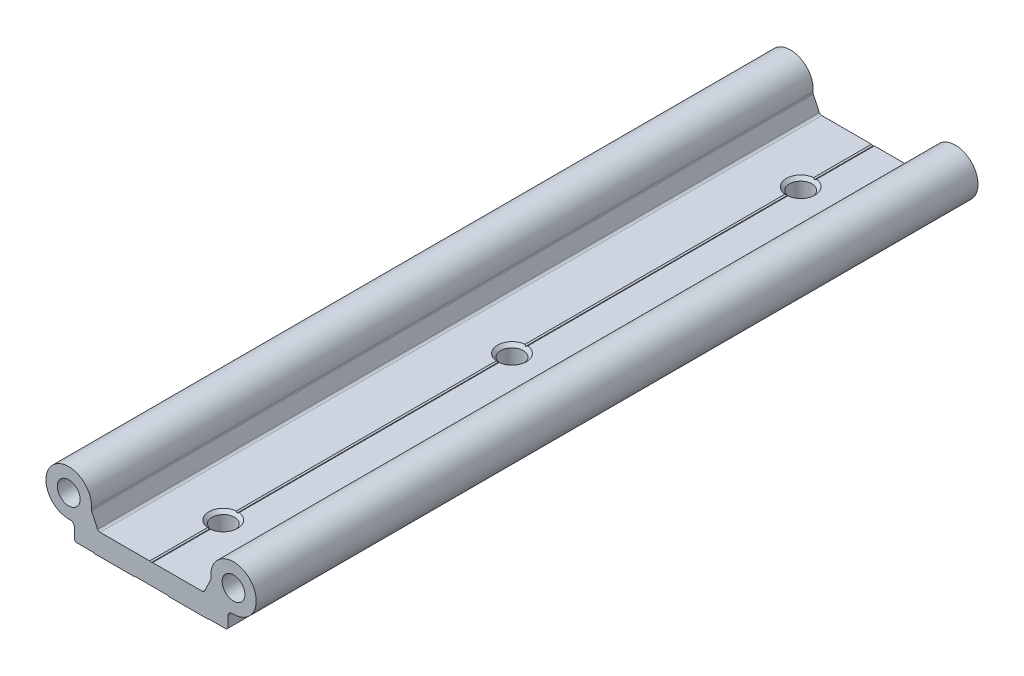
SolidWorks part; units mm, degrees
ref_plane "Front Plane" through (0, 0, 0) normal (0, 0, 1) x (1, 0, 0)
ref_plane "Top Plane" through (0, 0, 0) normal (0, 1, 0) x (1, 0, 0)
ref_plane "Right Plane" through (0, 0, 0) normal (1, 0, 0) x (0, 0, -1)
sketch "Model" plane through (0, 0, 0) normal (0, 0, 1) x (1, 0, 0)
  line L0 (0, 0.2) -> (0, 7.5) construction
  line L1 (0, 0.2) -> (0, 7.5) construction
  line L2 (0, 0.2) -> (0, 7.5) construction
  line L3 (0, 0.2) -> (0, 7.5) construction
  line L4 (-33, 14) -> (-25, 14) construction
  line L5 (25, 14) -> (33, 14) construction
  line L6 (-29, 22) -> (-29, 6) construction
  line L7 (-37, 14) -> (-21, 14) construction
  line L8 (29, 22) -> (29, 6) construction
  line L9 (21, 14) -> (37, 14) construction
  line L10 (-18.8438, 7.9819) -> (-20.9669, 12.5349)
  line L11 (6, 0) -> (5.8, 0.2)
  line L12 (-26.5, 0.2) -> (-27, 0.7)
  line L13 (-20, 0) -> (-20.2, 0.2)
  line L14 (0, 7.2113) -> (-0.5, 7.5)
  line L15 (6, 0) -> (20, 0)
  line L16 (-20, 0) -> (-6, 0)
  line L17 (-5.8, 0.2) -> (5.8, 0.2)
  line L18 (20.2, 0.2) -> (26.5, 0.2)
  line L19 (-26.5, 0.2) -> (-20.2, 0.2)
  line L20 (0.5, 7.5) -> (17.9885, 7.5)
  line L21 (-17.9885, 7.5) -> (-0.5, 7.5)
  line L22 (0, 7.2113) -> (0.5, 7.5)
  line L23 (20, 0) -> (20.2, 0.2)
  line L24 (-6, 0) -> (-5.8, 0.2)
  line L25 (26.5, 0.2) -> (27, 0.7)
  line L26 (18.8438, 7.9819) -> (20.9669, 12.5349)
  line L27 (-27, 0.7) -> (-27, 4.5132)
  line L28 (27, 0.7) -> (27, 4.5132)
  circle A0 centre (-29, 14) radius 4
  arc A1 (-21.0538, 13.0733) -> (-28.5789, 6.0111) centre (-29, 14) ccw
  arc A2 (-27, 4.5132) -> (-28.5789, 6.0111) centre (-28.5, 4.5132) ccw
  arc A3 (-21.0538, 13.0733) -> (-20.9669, 12.5349) centre (-20.0606, 12.9575) ccw
  arc A4 (-18.8438, 7.9819) -> (-17.9885, 7.5) centre (-17.9885, 8.5) ccw
  arc A5 (17.9885, 7.5) -> (18.8438, 7.9819) centre (17.9885, 8.5) ccw
  arc A6 (20.9669, 12.5349) -> (21.0538, 13.0733) centre (20.0606, 12.9575) ccw
  arc A7 (28.5789, 6.0111) -> (27, 4.5132) centre (28.5, 4.5132) ccw
  circle A8 centre (29, 14) radius 4
  arc A9 (28.5789, 6.0111) -> (21.0538, 13.0733) centre (29, 14) ccw
  dimension "D1" = 8
  dimension "D2" = 8
  dimension "D3" = 1.5
  dimension "D4" = 1
  dimension "D5" = 0.5
  dimension "D6" = 5.8
  dimension "D7" = 6
  dimension "D8" = 17.9885
  dimension "D9" = 18.8438
  dimension "D10" = 20
  dimension "D11" = 20.0606
  dimension "D12" = 20.9669
  dimension "D13" = 21.0538
  dimension "D14" = 26.5
  dimension "D15" = 27
  dimension "D16" = 4.5132
  dimension "D17" = 7.2113
extrude "Boss-Extrude1" add sketch "Model" along normal blind 254
hole_wizard "3/8-16 Tapped Hole1" positions "Sketch1" profile "Sketch2" tap size "3/8-16" standard "ANSI Inch" end condition through all
sketch "Sketch1" plane through (0, 7.5, 0) normal (0, 1, 0) x (1, 0, 0)
  line L0 (0, -254) -> (0, 0) construction
  line L1 (-0.5, 0) -> (-17.9885, 0) construction
  point P0 (0, -25.4)
  point P21 (0, -127)
  point P22 (0, -228.6)
  point P23 (0, -330.2)
  point P24 (0, -431.8)
  point P25 (0, -533.4)
  point P26 (0, -635)
  point P27 (0, -736.6)
  point P28 (0, -838.2)
  point P29 (0, -939.8)
  point P30 (0, -1041.4)
  point P31 (0, -1143)
  point P32 (0, -1244.6)
  point P33 (0, -1346.2)
  point P34 (0, -1447.8)
  point P35 (0, -1549.4)
  point P36 (0, -1651)
  point P37 (0, -1752.6)
  point P38 (0, -1854.2)
  point P39 (0, -1955.8)
  dimension "D1" = 25.4
  dimension "D2" = 20
sketch "Sketch2" plane through (0, 7.5, 25.4) normal (1, 0, 0) x (0, 0, 1)
  line L0 (0, 0) -> (0, 7.5)
  line L1 (0, 7.5) -> (3.9687, 7.5)
  line L2 (3.9687, 7.5) -> (3.9687, 1.1113)
  line L3 (3.9687, 1.1113) -> (5.08, 0)
  line L5 (5.08, 0) -> (0, 0)
  line L6 (-3.9687, 1.1112) -> (-5.08, 0) construction
  line L11 (0, -6.35) -> (0, 107.95) construction
  dimension "Thread Major Dia." = 7.9375
  dimension "Thru Tap Drill Depth" = 7.5
  dimension "Near C'Sink Dia." = 10.16
  dimension "Near C'Sink Angle" = 90
